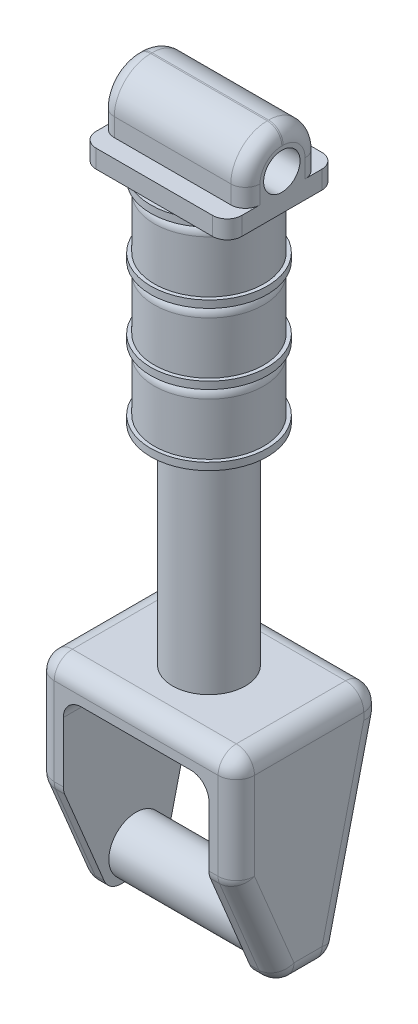
SolidWorks part; units mm, degrees
ref_plane "Front" through (0, 0, 0) normal (0, 0, 1) x (1, 0, 0)
ref_plane "Top" through (0, 0, 0) normal (0, 1, 0) x (1, 0, 0)
ref_plane "Right" through (0, 0, 0) normal (1, 0, 0) x (0, 0, -1)
sketch "Sketch1" plane through (0, 0, 0) normal (0, 0, 1) x (1, 0, 0)
  line L0 (0, -279.4) -> (38.1, -279.4) construction
  line L1 (76.2, -279.4) -> (-76.2, -279.4) construction
  line L2 (76.2, -279.4) -> (76.2, 279.4) construction
  line L3 (76.2, 279.4) -> (-76.2, 279.4) construction
  line L4 (-76.2, -279.4) -> (-76.2, 279.4) construction
  line L5 (76.2, -279.4) -> (-76.2, 279.4) construction
  line L6 (76.2, 279.4) -> (-76.2, -279.4) construction
  line L7 (38.1, -279.4) -> (38.1, -76.2) construction
  line L8 (38.1, -76.2) -> (-38.1, -76.2) construction
  line L9 (-38.1, -76.2) -> (-38.1, -279.4) construction
  line L10 (-38.1, -196.85) -> (-38.1, -158.75) construction
  line L11 (-50.8, -196.85) -> (-69.85, -196.85)
  line L12 (-69.85, -196.85) -> (-69.85, -44.45)
  line L13 (-69.85, -44.45) -> (69.85, -44.45)
  line L14 (69.85, -44.45) -> (69.85, -196.85)
  line L15 (69.85, -196.85) -> (50.8, -196.85)
  line L16 (50.8, -196.85) -> (50.8, -63.5)
  line L17 (50.8, -63.5) -> (-50.8, -63.5)
  line L18 (-50.8, -63.5) -> (-50.8, -196.85)
  point P0 (0, 0)
  dimension "D1" = 558.8
  dimension "D2" = 152.4
  dimension "D3" = 76.2
  dimension "D4" = 203.2
  dimension "D5" = 38.1
  dimension "D6" = 38.1
  dimension "D7" = 19.05
  dimension "D8" = 19.05
  dimension "D9" = 19.05
  dimension "D10" = 12.7
  dimension "D11" = 12.7
  dimension "D12" = 12.7
  dimension "D13" = 82.55
  dimension "D14" = 82.55
extrude "Boss-Extrude1" add sketch "Sketch1" against normal blind 101.6
sketch "Sketch2" plane through (69.85, 0, 0) normal (1, 0, 0) x (0, 0, -1)
  line L0 (101.6, -196.85) -> (0, -196.85) construction
  line L1 (0, -196.85) -> (0, -44.45) construction
  circle A0 centre (50.8, -177.8) radius 19.05
  dimension "D1" = 38.1
  dimension "D2" = 19.05
  dimension "D3" = 50.8
extrude "Boss-Extrude2" add sketch "Sketch2" against normal up to surface (120.65 mm away) up to face at (-50.8, -130.175, -50.8)
sketch "Sketch4" plane through (69.85, 0, 0) normal (1, 0, 0) x (0, 0, -1)
  line L0 (31.75, -196.85) -> (69.85, -196.85)
  line L1 (101.6, -196.85) -> (0, -196.85) construction
  line L3 (101.6, -196.85) -> (101.6, -44.45) construction
  line L4 (101.6, -63.5) -> (101.6, -196.85)
  line L5 (101.6, -196.85) -> (69.85, -196.85)
  line L6 (50.8, -44.45) -> (50.8, -233.0017) construction
  line L7 (101.6, -44.45) -> (0, -44.45) construction
  line L8 (69.85, -196.85) -> (101.6, -63.5)
  line L9 (31.75, -196.85) -> (0, -120.65)
  line L10 (0, -196.85) -> (0, -44.45) construction
  line L11 (0, -120.65) -> (0, -196.85)
  line L12 (0, -196.85) -> (31.75, -196.85)
  line M6 (0, -44.45) -> (0, -196.85)
  line M7 (0, -196.85) -> (101.6, -196.85)
  line M8 (101.6, -196.85) -> (101.6, -44.45)
  dimension "D1" = 38.1
  dimension "D2" = 31.75
  dimension "D3" = 19.05
extrude "Cut-Extrude1" cut sketch "Sketch4" against normal up to surface (139.7 mm away) contours L9 M7 M6 | L8 M7 M8 region at (69.85, -152.4, -91.0167) region at (69.85, -171.45, -10.5833) up to face at (-69.85, -120.65, -50.8)
fillet "Fillet1" radius 12.7 10 edges at (-50.8, -63.5, -50.8) (50.8, -63.5, -50.8) (0, -44.45, 0) (0, -44.45, -101.6) (60.325, -196.85, -31.75) (60.325, -196.85, -69.85) (-60.325, -196.85, -69.85) (-60.325, -196.85, -31.75) (-60.325, -120.65, 0) (60.325, -120.65, 0)
fillet "Fillet2" radius 12.7 22 edges at (-69.85, -120.6007, -0.2466) (-69.85, -156.0146, -14.7353) (-69.85, -194.717, -33.172) (-69.85, -196.85, -50.0177) (-69.85, -194.1161, -67.6906) (-69.85, -125.2958, -86.8867) (-69.85, -60.325, -101.6) (-69.85, -48.1697, -97.8803) (-69.85, -44.45, -50.8) (-69.85, -48.1697, -3.7197) (-69.85, -87.63, 0) (69.85, -48.1697, -97.8803) (69.85, -60.325, -101.6) (69.85, -125.2958, -86.8867) (69.85, -194.1161, -67.6906) (69.85, -196.85, -50.0177) (69.85, -194.717, -33.172) (69.85, -156.0146, -14.7353) (69.85, -120.6007, -0.2466) (69.85, -87.63, 0) (69.85, -48.1697, -3.7197) (69.85, -44.45, -50.8)
sketch "Sketch5" plane through (0, -44.45, 0) normal (0, 1, 0) x (1, 0, 0)
  circle A0 centre (0, 50.8) radius 25.4
  dimension "D1" = 50.8
extrude "Boss-Extrude3" add sketch "Sketch5" along normal blind 146.05
sketch "Sketch6" plane through (0, 101.6, 0) normal (0, 1, 0) x (1, 0, 0)
  circle A0 centre (0, 50.8) radius 40.64
  dimension "D1" = 81.28
extrude "Boss-Extrude4" add sketch "Sketch6" along normal blind 5.08
sketch "Sketch7" plane through (0, 106.68, 0) normal (0, 1, 0) x (1, 0, 0)
  circle A0 centre (0, 50.8) radius 38.1
  dimension "D1" = 76.2
extrude "Boss-Extrude5" add sketch "Sketch7" along normal blind 43.942
fillet "Fillet5" radius 7.62 1 edges at (0, 150.622, -12.7)
sketch "Sketch8" plane through (0, 150.622, 0) normal (0, 1, 0) x (1, 0, 0)
  circle A0 centre (0, 50.8) radius 40.64
  dimension "D1" = 81.28
extrude "Boss-Extrude6" add sketch "Sketch8" along normal blind 5.08
sketch "Sketch9" plane through (0, 155.702, 0) normal (0, 1, 0) x (1, 0, 0)
  circle A0 centre (0, 50.8) radius 38.1
  dimension "D1" = 76.2
extrude "Boss-Extrude7" add sketch "Sketch9" along normal blind 43.942
fillet "Fillet6" radius 7.62 1 edges at (0, 199.644, -12.7)
sketch "Sketch10" plane through (0, 199.644, 0) normal (0, 1, 0) x (1, 0, 0)
  circle A0 centre (0, 50.8) radius 40.64
  dimension "D1" = 81.28
extrude "Boss-Extrude8" add sketch "Sketch10" along normal blind 5.08
sketch "Sketch11" plane through (0, 204.724, 0) normal (0, 1, 0) x (1, 0, 0)
  circle A0 centre (0, 50.8) radius 38.1
  dimension "D1" = 76.2
extrude "Boss-Extrude9" add sketch "Sketch11" along normal blind 43.942
fillet "Fillet7" radius 7.62 1 edges at (0, 248.666, -12.7)
sketch "Sketch12" plane through (0, 248.666, 0) normal (0, 1, 0) x (1, 0, 0)
  circle A0 centre (0, 50.8) radius 40.64
  dimension "D1" = 81.28
extrude "Boss-Extrude10" add sketch "Sketch12" along normal blind 5.08
sketch "Sketch13" plane through (0, 0, 0) normal (1, 0, 0) x (0, 0, -1)
  line L0 (50.8, 253.746) -> (12.7, 253.746)
  line L1 (91.44, 253.746) -> (10.16, 253.746) construction
  line L2 (12.7, 253.746) -> (12.7, 266.446)
  line L3 (12.7, 266.446) -> (25.4, 266.446)
  line L4 (25.4, 266.446) -> (25.4, 279.146)
  line L5 (50.8, 304.546) -> (51.7783, 304.546)
  line L6 (77.1783, 279.146) -> (77.1783, 266.446)
  line L7 (77.1783, 266.446) -> (88.9, 266.446)
  line L8 (88.9, 266.446) -> (88.9, 253.746)
  line L9 (88.9, 253.746) -> (50.8, 253.746)
  line L10 (50.8, 253.746) -> (50.8, 279.146) construction
  circle A0 centre (50.8, 279.146) radius 12.7
  arc A1 (50.8, 304.546) -> (25.4, 279.146) centre (50.8, 279.146) ccw
  arc A2 (77.1783, 279.146) -> (51.7783, 304.546) centre (51.7783, 279.146) ccw
  point P15 (25.4, 304.546)
  point P18 (51.7783, 304.546)
  dimension "D7" = 25.4
  dimension "D8" = 25.4
  dimension "D9" = 25.4
  dimension "D11" = 25.4
  dimension "D10" = 25.4
  dimension "D1" = 12.7
  dimension "D2" = 12.7
  dimension "D3" = 38.1
  dimension "D4" = 38.1
  dimension "D5" = 38.1
  dimension "D6" = 25.4
extrude "Boss-Extrude11" add sketch "Sketch13" along normal blind 50.8 and the other way blind 50.8
fillet "Fillet3" radius 10.16 4 edges at (50.8, 260.096, -12.7) (-50.8, 260.096, -12.7) (-50.8, 260.096, -88.9) (50.8, 260.096, -88.9)
fillet "Fillet4" radius 10.16 10 edges at (-50.8, 272.796, -77.1783) (-50.8, 272.796, -25.4) (-50.8, 297.1065, -32.8395) (-50.8, 304.546, -51.2891) (50.8, 272.796, -77.1783) (50.8, 297.1065, -69.7388) (50.8, 304.546, -51.2891) (50.8, 272.796, -25.4) (-50.8, 297.1065, -69.7388) (50.8, 297.1065, -32.8395)
